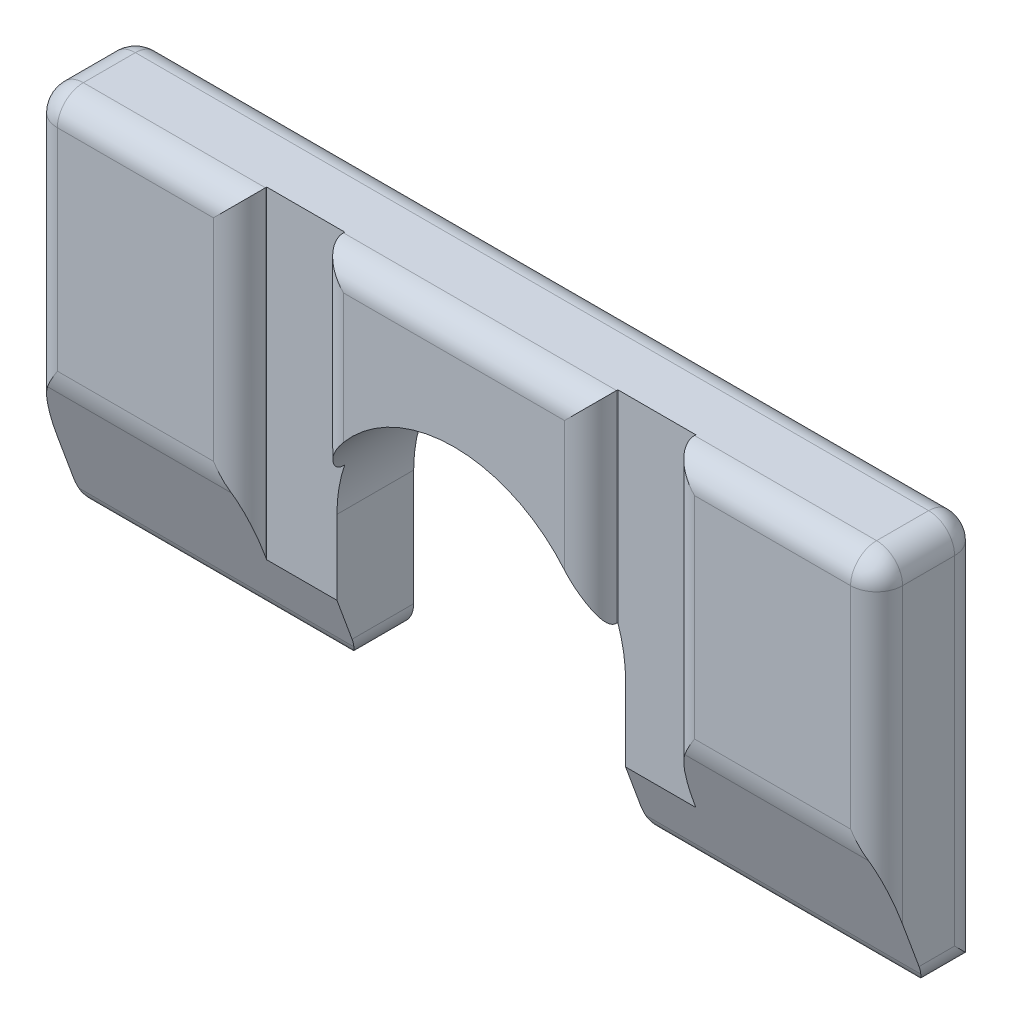
SolidWorks part; units mm, degrees
ref_plane "前视基准面" through (0, 0, 0) normal (0, 0, 1) x (1, 0, 0)
ref_plane "上视基准面" through (0, 0, 0) normal (0, 1, 0) x (1, 0, 0)
ref_plane "右视基准面" through (0, 0, 0) normal (1, 0, 0) x (0, 0, -1)
sketch "草图1" plane through (0, 0, 0) normal (0, 0, 1) x (1, 0, 0)
  line L0 (-11.1, -4.1) -> (-11.1, -15)
  line L1 (-32.5, 15) -> (32.5, 15)
  line L2 (-32.5, 15) -> (-32.5, -15)
  line L3 (-32.5, -15) -> (-11.1, -15)
  line L4 (32.5, 15) -> (32.5, -15)
  line L5 (0, -15) -> (0, 15) construction
  line L6 (-32.5, 0) -> (32.5, 0) construction
  line L7 (11.1, -4.1) -> (11.1, -15)
  line L8 (-11.1, -15) -> (0, -15) construction
  line L9 (11.1, -15) -> (32.5, -15)
  line L10 (0, -15) -> (11.1, -15) construction
  arc A0 (11.1, -4.1) -> (-11.1, -4.1) centre (0, -4.1) ccw
  arc A1 (-11.1, -4.1) -> (0, -15.2) centre (0, -4.1) ccw construction
  arc A2 (0, -15.2) -> (11.1, -4.1) centre (0, -4.1) ccw construction
  point P0 (0, 0)
  dimension "D3" = 22.2
  dimension "D1" = 65
  dimension "D2" = 30
  dimension "D4" = 19.1
extrude "凸台-拉伸1" add sketch "草图1" along normal blind 8
sketch "草图3" plane through (0, 0, 8) normal (0, 0, 1) x (1, 0, 0)
  line L0 (0, 15) -> (0, -49985) construction
  line L1 (32.5, 15) -> (-32.5, 15) construction
  line L2 (-16.5, 15) -> (-16.5, -15)
  line L3 (-32.5, -15) -> (-11.1, -15) construction
  line L4 (-16.5, -15) -> (-10.5, -15)
  line L5 (-10.5, -15) -> (-10.5, 15)
  line L6 (-10.5, 15) -> (-16.5, 15)
  line L7 (-13.5, 15) -> (-13.5, -15) construction
  line L8 (16.5, -15) -> (10.5, -15)
  line L9 (16.5, 15) -> (16.5, -15)
  line L10 (10.5, 15) -> (16.5, 15)
  line L11 (10.5, -15) -> (10.5, 15)
  point P4 (0, 15)
  dimension "D1" = 6
  dimension "D2" = 13.5
extrude "切除-拉伸2" cut sketch "草图3" against normal blind 2.1
sketch "草图2" plane through (32.5, 0, 0) normal (1, 0, 0) x (0, 0, -1)
  line L0 (-8, -4.1) -> (-4, -15)
  line L2 (-8, -15) -> (0, -15) construction
  line L6 (-5.9, -4.1) -> (0, -4.1) construction
  line L7 (-8, -4.1) -> (0, -4.1) construction
  line L12 (0, -15) -> (0, 15)
  line L13 (0, 15) -> (-8, 15)
  line L14 (-8, 15) -> (-8, -15)
  line L15 (-8, -15) -> (0, -15)
  line L16 (0, -15) -> (0, 15)
  line L17 (0, 15) -> (-8, 15)
  line L18 (-8, 15) -> (-8, -15)
  line L19 (-8, -15) -> (0, -15)
  line M7 (-8, 15) -> (-8, -15)
  line M8 (-8, -15) -> (0, -15)
  dimension "D2" = 0
extrude "切除-拉伸3" cut sketch "草图2" against normal through all contours L0 M7 M8
fillet "圆角1" radius 2 20 edges at (-16.5, 5.45, 8) (16.5, 5.45, 8) (10.5, 7.25, 8) (-10.5, 7.25, 8) (-24.5, 15, 8) (0, 15, 8) (-32.5, 15, 4) (-32.5, 5.45, 8) (-32.5, 0, 0) (0, 15, 0) (32.5, 0, 0) (32.5, 5.45, 8) (32.5, 15, 4) (24.5, 15, 8) (32.5, -15, 2) (21.8, -15, 4) (11.1, -15, 2) (-32.5, -15, 2) (-11.1, -15, 2) (-21.8, -15, 4)
fillet "圆角2" radius 5 2 edges at (24.5, -4.1, 8) (-24.5, -4.1, 8)
